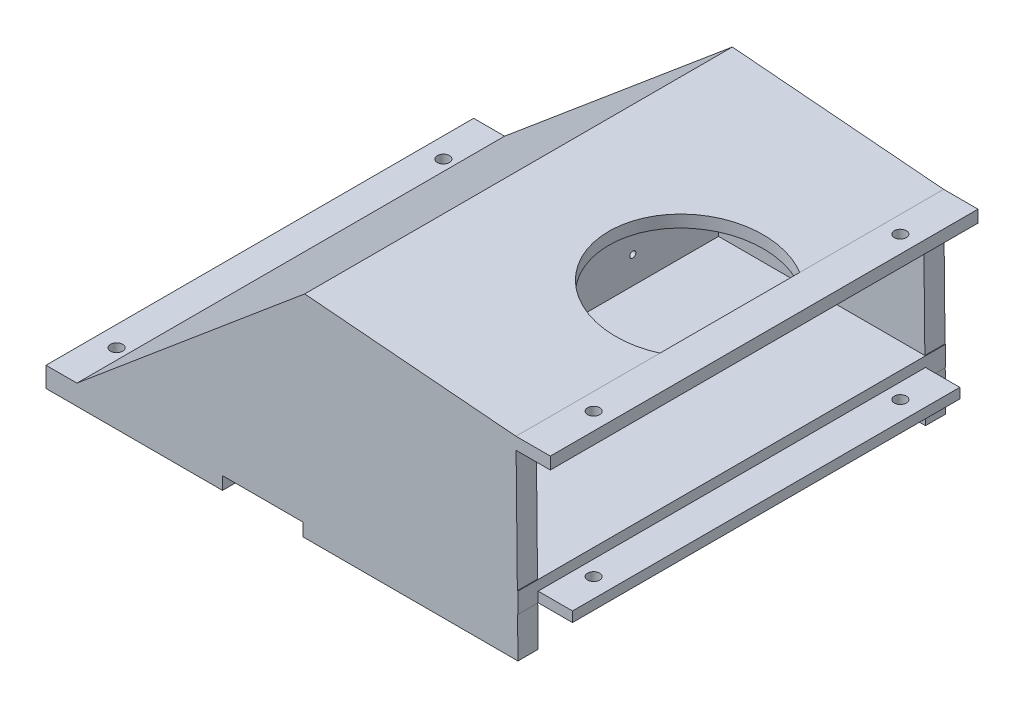
SolidWorks part; units mm, degrees
ref_plane "Front Plane" through (0, 0, 0) normal (0, 0, 1) x (1, 0, 0)
ref_plane "Top Plane" through (0, 0, 0) normal (0, 1, 0) x (1, 0, 0)
ref_plane "Right Plane" through (0, 0, 0) normal (1, 0, 0) x (0, 0, -1)
sketch "Sketch1" plane through (0, 0, 0) normal (0, 0, 1) x (1, 0, 0)
  line L2 (0, 0) -> (0, -6)
  line L6 (-234.6631, -86) -> (-250, -86)
  line L7 (-250, -86) -> (-250, -96)
  line L8 (-250, -96) -> (-230, -96)
  line L12 (-206.1649, -76) -> (0.9775, -76)
  line L16 (-16.0425, -66) -> (-118.6219, -66)
  line L20 (-16.0425, -66) -> (-16.0425, -71)
  line L21 (-16.0425, -71) -> (0.9775, -71)
  line L22 (0.9775, -71) -> (0.9775, -76)
  line L26 (0.9775, -66) -> (-92.0225, -66) construction
  line L27 (0.9775, -66) -> (0.9775, -13.5) construction
  line L28 (0.9775, -13.5) -> (-92.0225, -13.5) construction
  line L29 (-92.0225, -66) -> (-92.0225, -13.5) construction
  line L30 (-17.02, -6) -> (-118.6219, 2.463)
  line L31 (-118.6219, -1) -> (-99.8219, -1) construction
  line L32 (-118.6219, -1) -> (-118.6219, -66) construction
  line L33 (-118.6219, -66) -> (-99.8219, -66) construction
  line L34 (-99.8219, -1) -> (-99.8219, -66) construction
  line L39 (-17.02, -6) -> (0, -6)
  line L41 (-118.6219, 2.463) -> (-118.6219, -66)
  line L44 (-138.6219, -19.3246) -> (-138.6219, -66)
  line L45 (-138.6219, -66) -> (-194.2474, -66)
  line L46 (0, 0) -> (-17.02, 0)
  line L48 (-230, -96) -> (-206.1649, -76)
  line L49 (-17.02, 0) -> (-121.7736, 8.7256)
  line L50 (-234.6631, -86) -> (-121.7736, 8.7256)
  line L51 (-194.2474, -66) -> (-138.6219, -19.3246)
  point P13 (-250, -91)
  point P18 (0, -3)
  dimension "D1" = 250
  dimension "D2" = 20
  dimension "D3" = 20
  dimension "D4" = 10
  dimension "D5" = 5
  dimension "D6" = 6
  dimension "D7" = 20
  dimension "D8" = 5
  dimension "D9" = 65
  dimension "D10" = 52.5
  dimension "D11" = 40
  dimension "D12" = 93
  dimension "D13" = 18.8
  dimension "D14" = 65
  dimension "D18" = 17.02
extrude "Boss-Extrude1" add sketch "Sketch1" along normal blind 212
sketch "Sketch2" plane through (0, -76, 0) normal (0, -1, 0) x (1, 0, 0)
  line L1 (0.9775, 212) -> (-16.0425, 212)
  line L2 (0.9775, 212) -> (0.9775, 202)
  line L3 (0.9775, 202) -> (-16.0425, 202)
  line L4 (-16.0425, 212) -> (-16.0425, 202)
  line L5 (0.9775, 0) -> (-16.0425, 0)
  line L6 (0.9775, 0) -> (0.9775, 10)
  line L7 (0.9775, 10) -> (-16.0425, 10)
  line L8 (-16.0425, 0) -> (-16.0425, 10)
  dimension "D1" = 10
  dimension "D2" = 17.02
extrude "Cut-Extrude1" cut sketch "Sketch2" against normal up to next
sketch "Sketch3" plane through (-118.6219, 0, 0) normal (1, 0, 0) x (0, 0, -1)
  line L1 (-163.5, -0.037) -> (-48.5, -0.037) construction
  line L2 (-163.5, -0.037) -> (-163.5, -65.037) construction
  line L3 (-163.5, -65.037) -> (-48.5, -65.037) construction
  line L4 (-48.5, -0.037) -> (-48.5, -65.037) construction
  line L6 (-212, 2.463) -> (0, 2.463) construction
  line L7 (-212, -66) -> (-212, 2.463) construction
  line L8 (-106, -65.037) -> (-106, -6) construction
  circle A0 centre (-159.5, -12.537) radius 1.5
  circle A1 centre (-159.5, -52.537) radius 1.5
  circle A2 centre (-52.5, -52.537) radius 1.5
  circle A3 centre (-52.5, -12.537) radius 1.5
  dimension "D1" = 3
  dimension "D2" = 3
  dimension "D7" = 4
  dimension "D3" = 115
  dimension "D4" = 65
  dimension "D5" = 2.5
  dimension "D6" = 48.5
  dimension "D8" = 12.5
  dimension "D9" = 12.5
extrude "Cut-Extrude2" cut sketch "Sketch3" against normal blind 15
sketch "Sketch4" plane through (0, -86, 0) normal (0, 1, 0) x (1, 0, 0)
  line L0 (-250, -106) -> (-234.6631, -106) construction
  line L1 (-250, -212) -> (-250, 0) construction
  line L2 (-234.6631, -212) -> (-234.6631, 0) construction
  line L3 (-234.6631, 0) -> (-250, 0) construction
  circle A0 centre (-240, -25) radius 3
  circle A1 centre (-240, -187) radius 3
  dimension "D1" = 6
  dimension "D2" = 25
  dimension "D3" = 10
extrude "Cut-Extrude3" cut sketch "Sketch4" against normal blind 15
sketch "Sketch5" plane through (0, -66, 0) normal (0, 1, 0) x (1, 0, 0)
  line L0 (-118.6219, -212) -> (-118.6219, 0) construction
  line L1 (-113.6219, -176.8118) -> (-83.6219, -176.8118)
  line L2 (-113.6219, -176.8118) -> (-113.6219, -191.8118)
  line L3 (-113.6219, -191.8118) -> (-83.6219, -191.8118)
  line L4 (-83.6219, -176.8118) -> (-83.6219, -191.8118)
  dimension "D1" = 15
  dimension "D2" = 5
  dimension "D3" = 30
extrude "Cut-Extrude4" cut sketch "Sketch5" against normal blind 15
sketch "Sketch6" plane through (0, 0, 0) normal (0, 1, 0) x (1, 0, 0)
  line L0 (0, 0) -> (-17.02, 0) construction
  line L1 (-17.02, -212) -> (-17.02, 0) construction
  line L2 (-17.02, -106) -> (0.9775, -106) construction
  line L3 (0.9775, -202) -> (0.9775, -10) construction
  circle A0 centre (-8.52, -30) radius 3
  circle A1 centre (-8.52, -182) radius 3
  dimension "D1" = 6
  dimension "D2" = 30
  dimension "D3" = 8.5
extrude "Cut-Extrude5" cut sketch "Sketch6" against normal through all both and the other way through all
sketch "Sketch7" plane through (0, 0, 212) normal (0, 0, 1) x (1, 0, 0)
  line L10 (-17.02, 0) -> (-121.7736, 8.7256) construction
  line L11 (-17.02, 0) -> (-121.7736, 8.7256)
  line L13 (-250, -86) -> (-250, -96) construction
  line L14 (-234.6631, -86) -> (-250, -86) construction
  line L15 (-121.7736, 8.7256) -> (-234.6631, -86) construction
  line L16 (-250, -86) -> (-250, -96)
  line L17 (-234.6631, -86) -> (-250, -86)
  line L18 (-121.7736, 8.7256) -> (-234.6631, -86)
  line L19 (-250, -96) -> (-16.0425, -96)
  line L20 (-16.0425, -96) -> (-17.02, 0)
extrude "Boss-Extrude2" add sketch "Sketch7" against normal blind 10
sketch "Sketch8" plane through (0, 0, 0) normal (0, 0, -1) x (-1, 0, 0)
  line L0 (250, -96) -> (230, -96) construction
  line L1 (250, -86) -> (250, -96) construction
  line L2 (234.6631, -86) -> (250, -86) construction
  line L3 (121.7736, 8.7256) -> (234.6631, -86) construction
  line L4 (17.02, 0) -> (121.7736, 8.7256) construction
  line L5 (250, -96) -> (230, -96)
  line L6 (250, -86) -> (250, -96)
  line L7 (234.6631, -86) -> (250, -86)
  line L8 (121.7736, 8.7256) -> (234.6631, -86)
  line L9 (17.02, 0) -> (121.7736, 8.7256)
  line L10 (230, -96) -> (16.0425, -96)
  line L11 (16.0425, -96) -> (17.02, 0)
extrude "Boss-Extrude3" add sketch "Sketch8" against normal blind 10
sketch "Sketch9" plane through (0, 0, 212) normal (0, 0, 1) x (1, 0, 0)
  line L0 (-250, -96) -> (-16.0425, -96) construction
  line L1 (-162.5, -96) -> (-122.5, -96)
  line L2 (-162.5, -96) -> (-162.5, -89.65)
  line L3 (-162.5, -89.65) -> (-122.5, -89.65)
  line L4 (-122.5, -96) -> (-122.5, -89.65)
  line L5 (-250, -86) -> (-250, -96) construction
  dimension "D1" = 87.5
  dimension "D2" = 40
  dimension "D3" = 6.35
extrude "Cut-Extrude6" cut sketch "Sketch9" against normal through all both
sketch "Sketch10" plane through (0, 0, 0) normal (0, 1, 0) x (1, 0, 0)
  line L0 (-17.02, -212) -> (-17.02, 0) construction
  line L1 (-17.02, -140.639) -> (-17.02, -71.361)
  line L2 (-121.7736, -212) -> (-121.7736, 0) construction
  line L4 (-17.02, 0) -> (-121.7736, 0) construction
  arc A1 (-17.02, -71.361) -> (-17.02, -140.639) centre (-37.0236, -106) ccw
  dimension "D1" = 84.75
  dimension "D2" = 80
  dimension "D3" = 106
extrude "Cut-Extrude9" cut sketch "Sketch10" against normal blind 27 and the other way blind 25
